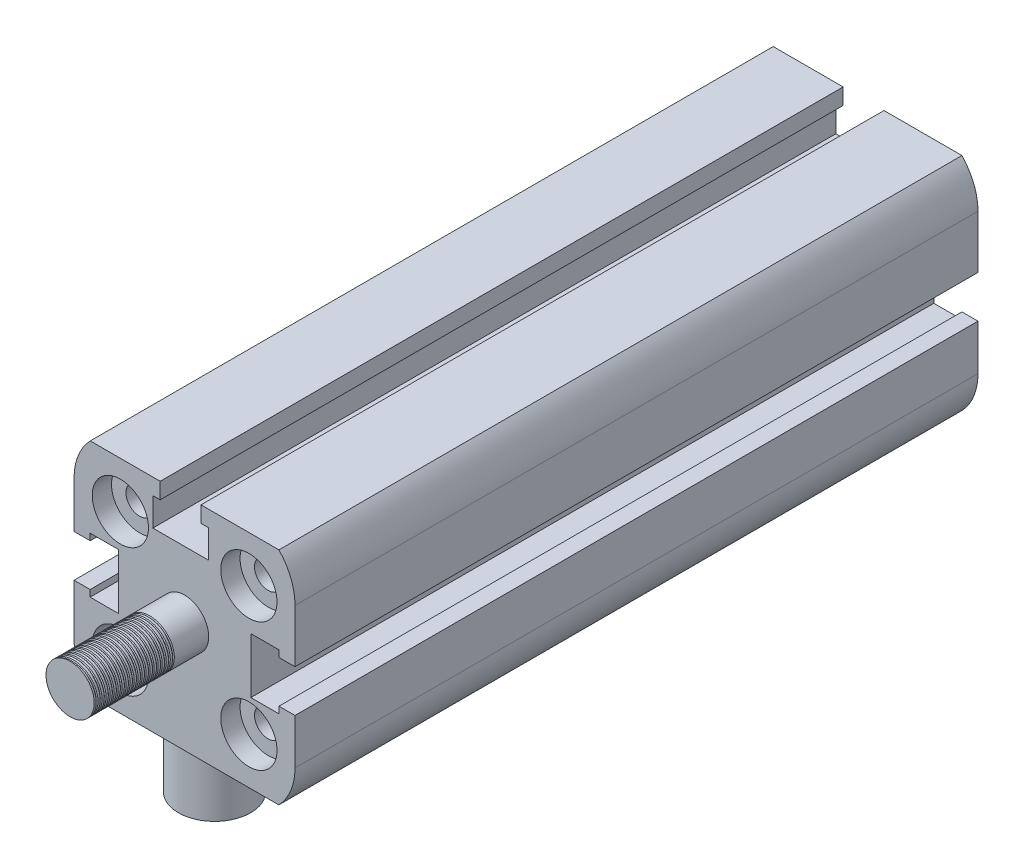
SolidWorks part; units mm, degrees
ref_plane "Ebene vorne" through (0, 0, 0) normal (0, 0, 1) x (1, 0, 0)
ref_plane "Ebene oben" through (0, 0, 0) normal (0, 1, 0) x (1, 0, 0)
ref_plane "Ebene rechts" through (0, 0, 0) normal (1, 0, 0) x (0, 0, -1)
sketch "Skizze1" plane through (0, 0, 0) normal (0, 0, 1) x (1, 0, 0)
  line L0 (-11.7424, 13.7458) -> (11.7424, 13.7458)
  line L1 (13.7424, 8.7458) -> (13.7424, -8.7627)
  line L2 (11.7273, -13.7542) -> (-11.7576, -13.7542)
  line L3 (-13.7576, -8.7542) -> (-13.7576, 8.7542)
  arc A0 (13.7424, 8.7458) -> (11.7424, 13.7458) centre (6.4924, 8.7458) ccw
  arc A1 (13.7424, -8.7627) -> (11.7273, -13.7542) centre (6.5528, -8.7627) cw
  arc A2 (-13.7576, -8.7542) -> (-11.7576, -13.7542) centre (-6.5076, -8.7542) ccw
  arc A3 (-13.7576, 8.7542) -> (-11.7424, 13.7458) centre (-6.5679, 8.7542) cw
  point P18 (0, 13.7458)
  point P19 (-13.7576, 0)
  dimension "D1" = 27.5
  dimension "D2" = 27.5
  dimension "D3" = 5
  dimension "D4" = 2
  dimension "D5" = 13.0604
extrude "Aufsatz-Linear austragen1" add sketch "Skizze1" along normal blind 85
sketch "Skizze3" plane through (0, 0, 85) normal (0, 0, 1) x (1, 0, 0)
  line L0 (-3.0424, 13.7458) -> (-3.0424, 11.7458)
  line L1 (11.7424, 13.7458) -> (-11.7424, 13.7458) construction
  line L2 (-3.0424, 11.7458) -> (-3.95, 11.7458)
  line L3 (-3.95, 11.7458) -> (-3.95, 8.2458)
  line L4 (-3.95, 8.2458) -> (2.95, 8.2458)
  line L5 (2.95, 8.2458) -> (2.95, 11.7458)
  line L6 (2.95, 11.7458) -> (2.0424, 11.7458)
  line L7 (2.0424, 11.7458) -> (2.0424, 13.7458)
  line L8 (13.7424, -3.1042) -> (11.7424, -3.1042)
  line L9 (13.7424, -8.7627) -> (13.7424, 8.7458) construction
  line L10 (11.7424, -3.1042) -> (11.7424, -3.9292)
  line L11 (11.7424, -3.9292) -> (8.2424, -3.9292)
  line L12 (8.2424, -3.9292) -> (8.2424, 2.9708)
  line L13 (8.2424, 2.9708) -> (11.7424, 2.9708)
  line L14 (11.7424, 2.9708) -> (11.7424, 2.1458)
  line L15 (11.7424, 2.1458) -> (13.7424, 2.1458)
  line L16 (13.7424, 2.1458) -> (13.7424, -3.1042)
  line L17 (2.0424, 13.7458) -> (-3.0424, 13.7458)
  line L18 (-11.7576, -13.7542) -> (11.7273, -13.7542) construction
  line L19 (-13.7576, 2.9708) -> (-11.7576, 2.9708)
  line L20 (-13.7576, 8.7542) -> (-13.7576, -8.7542) construction
  line L21 (-11.7576, 2.9708) -> (-11.7576, 3.7958)
  line L22 (-11.7576, 3.7958) -> (-8.2576, 3.7958)
  line L23 (-8.2576, 3.7958) -> (-8.2576, -3.1042)
  line L24 (-8.2576, -3.1042) -> (-11.7576, -3.1042)
  line L25 (-11.7576, -3.1042) -> (-11.7576, -2.2792)
  line L26 (-11.7576, -2.2792) -> (-13.7576, -2.2792)
  line L27 (-13.7576, -2.2792) -> (-13.7576, 2.9708)
  dimension "D1" = 9.7
  dimension "D2" = 8.7
  dimension "D3" = 6.9
  dimension "D4" = 3.5
  dimension "D5" = 2
  dimension "D6" = 10.65
  dimension "D7" = 11.6
extrude "Schnitt-Linear austragen1" cut sketch "Skizze3" against normal through all
hole_wizard "Stirnsenkung für M3 Flachkopfschraube mit Schlitz1" positions "Skizze4" profile "Skizze5" counterbore size "M3" standard "DIN"
sketch "Skizze4" plane through (0, 0, 85) normal (0, 0, 1) x (1, 0, 0)
  point P0 (8, 8)
  point P2 (-8, -8)
  point P16 (-8, 8)
  point P18 (8, -8)
  dimension "D1" = 16
  dimension "D2" = 16
  dimension "D3" = 8
  dimension "D4" = 8
sketch "Skizze5" plane through (8, 8, 85) normal (1, 0, 0) x (0, -1, 0)
  line L0 (0, 0) -> (0, 21.0215)
  line L1 (0, 21.0215) -> (1.7, 20)
  line L2 (1.7, 20) -> (1.7, 2.4)
  line L3 (1.7, 2.4) -> (3.5, 2.4)
  line L4 (3.5, 2.4) -> (3.5, 0)
  line L5 (3.5, 0) -> (0, 0)
  line L10 (0, 21.0215) -> (-1.7, 20) construction
  line L11 (0, -6.35) -> (0, 107.95) construction
  dimension "Bohrerdurchmesser" = 3.4
  dimension "Bohrungstiefe" = 20
  dimension "Senkdurchmesser2" = 7
  dimension "Senktiefe2" = 2.4
  dimension "Spitzenwinkel" = 118
sketch "Skizze8" plane through (0, 0, 85) normal (0, 0, 1) x (1, 0, 0)
  circle A0 centre (0, 0) radius 3
extrude "Aufsatz-Linear austragen2" add sketch "Skizze8" along normal blind 14.25
thread "Gewinde1" pitch 0.25 method cut profile "Gewindeprofil1" start angle 0, offset 0, length 10, pitch 0.5, diameter 6
ref_plane "Ebene1" through (-3, 0, 99.25) normal (0, -1, 0) x (-1, 0, 0)
sketch "Gewindeprofil1" plane through (-3, 0, 99.25) normal (0, -1, 0) x (-1, 0, 0)
  line L0 (0, 0) -> (0, 0.25) construction
  line L11 (0, 0) -> (0, 0.2187)
  line L12 (0, 0.2187) -> (-0.1353, 0.1406)
  line L13 (-0.1353, 0.1406) -> (-0.1353, 0.0781)
  line L15 (-0.1353, 0.0781) -> (0, 0)
  line L17 (-0.1353, 0.1094) -> (0, 0.1094) construction
  point P2 (0, 0)
  dimension "Pitch" = 0.25
  dimension "Profile_Angle" = 60
  dimension "Profile_Land" = 0.0625
  dimension "Profile_Height" = 0.1353
sketch "Skizze17" plane through (0, 0, 0) normal (0, 0, -1) x (-1, 0, 0)
  circle A0 centre (0, 0) radius 4.5
extrude "Schnitt-Linear austragen2" cut sketch "Skizze17" against normal blind 2
ref_plane "Ebene2" through (0, 0, 42.5) normal (0, 0, 1) x (1, 0, 0)
mirror "Spiegeln1" about plane through (0, 0, 42.5) normal (0, 0, 1) of "Stirnsenkung für M3 Flachkopfschraube mit Schlitz1"
sketch "Skizze18" plane through (0, -13.7542, 0) normal (0, -1, 0) x (1, 0, 0)
  line L0 (11.7273, 85) -> (11.7273, 0) construction
  line L1 (-11.7576, 0) -> (11.7273, 0) construction
  line L2 (-11.7576, 85) -> (11.7273, 85) construction
  circle A0 centre (-2.2727, 6) radius 4.5
  circle A1 centre (-2.2727, 79) radius 4.5
  point P0 (-2.2727, 6)
  point P1 (-2.2727, 79)
  dimension "D4" = 9
  dimension "D1" = 14
  dimension "D2" = 6
  dimension "D3" = 6
extrude "Aufsatz-Linear austragen3" add sketch "Skizze18" along normal blind 8.6 contours A0 | A1
